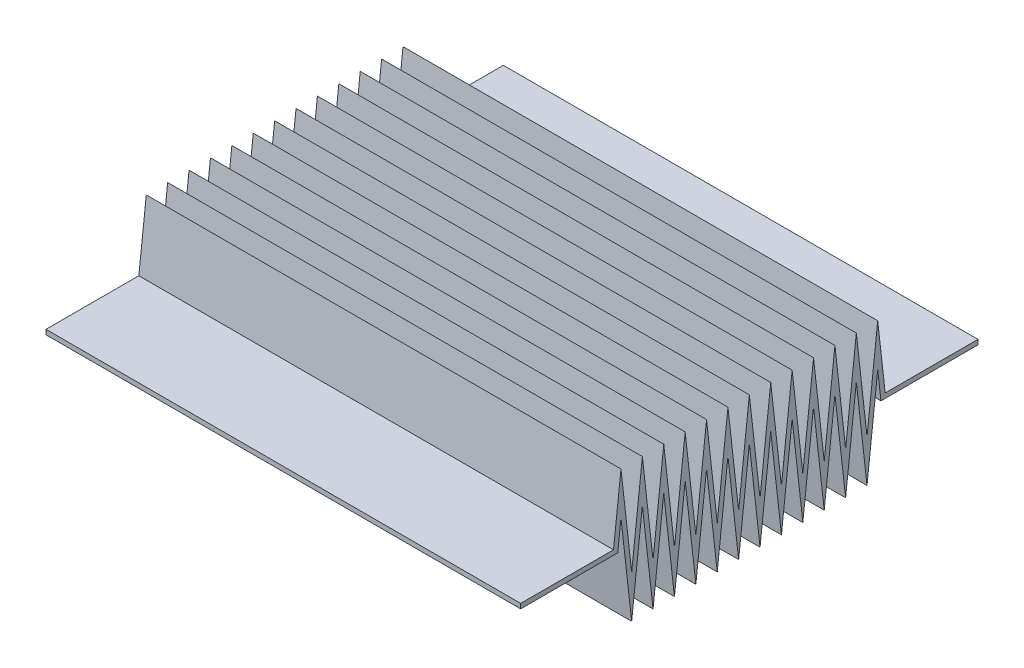
SolidWorks part; units mm, degrees
ref_plane "Front Plane" through (0, 0, 0) normal (0, 0, 1) x (1, 0, 0)
ref_plane "Top Plane" through (0, 0, 0) normal (0, 1, 0) x (1, 0, 0)
ref_plane "Right Plane" through (0, 0, 0) normal (1, 0, 0) x (0, 0, -1)
sketch "Sketch2" plane through (0, 0, 0) normal (0, 0, 1) x (1, 0, 0)
  line L1 (-27.5, 10) -> (27.5, 10)
  line L2 (-27.5, 10) -> (-27.5, 0)
  line L3 (-27.5, 0) -> (27.5, 0)
  line L4 (27.5, 10) -> (27.5, 0)
  point P4 (0, 0)
  dimension "D1" = 10
  dimension "D2" = 55
sketch "Sketch3" plane through (0, 0, 0) normal (1, 0, 0) x (0, 0, -1)
  line L0 (0, 10) -> (48.1702, 10) construction
  line L1 (0, 0) -> (48.1702, 0) construction
  line L3 (10, 5) -> (10.5634, 10)
  line L4 (10.5634, 10) -> (11.6902, 0)
  line L5 (11.6902, 0) -> (12.817, 10)
  line L6 (12.817, 10) -> (13.9438, 0)
  line L7 (13.9438, 0) -> (15.0706, 10)
  line L8 (15.0706, 10) -> (16.1974, 0)
  line L9 (16.1974, 0) -> (17.3242, 10)
  line L10 (17.3242, 10) -> (18.4511, 0)
  line L11 (18.4511, 0) -> (19.5779, 10)
  line L12 (19.5779, 10) -> (20.7047, 0)
  line L13 (20.7047, 0) -> (21.8315, 10)
  line L14 (21.8315, 10) -> (22.9583, 0)
  line L15 (22.9583, 0) -> (24.0851, 10)
  line L16 (24.0851, 10) -> (25.2119, 0)
  line L17 (25.2119, 0) -> (26.3387, 10)
  line L18 (26.3387, 10) -> (27.4655, 0)
  line L19 (0, 10) -> (0, 0) construction
  line L20 (27.4655, 0) -> (28.5923, 10)
  line L21 (28.5923, 10) -> (29.7191, 0)
  line L22 (29.7191, 0) -> (30.8459, 10)
  line L23 (30.8459, 10) -> (31.9727, 0)
  line L24 (31.9727, 0) -> (33.0996, 10)
  line L25 (33.0996, 10) -> (34.2264, 0)
  line L26 (34.2264, 0) -> (35.3532, 10)
  line L27 (35.3532, 10) -> (36.48, 0)
  line L28 (36.48, 0) -> (37.6068, 10)
  line L29 (37.6068, 10) -> (38.1702, 5)
  line L30 (48.1702, 10) -> (48.1702, 0) construction
  line L31 (10, 5) -> (0, 5)
  line L32 (38.1702, 5) -> (48.1702, 5)
  line L33 (48.1702, -12.3958) -> (48.1702, -19.8536) construction
  dimension "D2" = 10
  dimension "D1" = 10
  dimension "D3" = 10
extrude "Extrude-Thin1" add sketch "Sketch3" against normal mid plane 50 thin thin type mid plane wall 0.5
